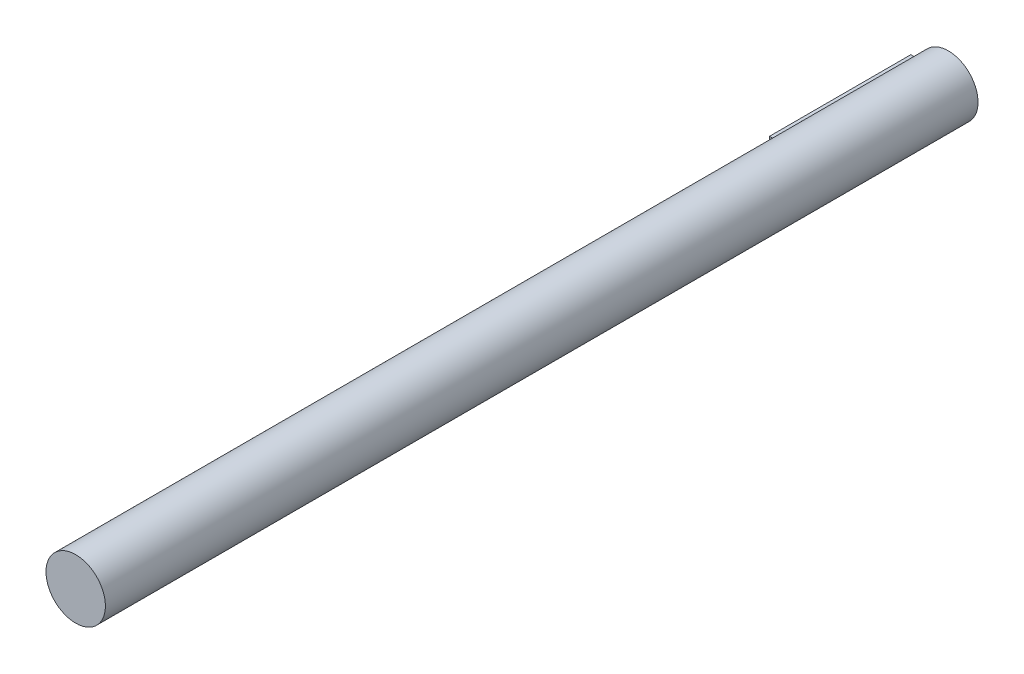
SolidWorks part; units mm, degrees
ref_plane "Front Plane" through (0, 0, 0) normal (0, 0, 1) x (1, 0, 0)
ref_plane "Top Plane" through (0, 0, 0) normal (0, 1, 0) x (1, 0, 0)
ref_plane "Right Plane" through (0, 0, 0) normal (1, 0, 0) x (0, 0, -1)
sketch "Sketch1" plane through (0, 0, 0) normal (0, 0, 1) x (1, 0, 0)
  line L0 (0, 0) -> (0, 3.175)
  line L1 (0, 3.175) -> (-15.621, 3.175)
  line L2 (-15.621, 3.175) -> (-15.621, -2.921)
  line L3 (-15.621, -2.921) -> (0, -2.921)
  line L4 (0, -2.921) -> (0, 0)
  circle A0 centre (0, 0) radius 12.3825
  dimension "D1" = 24.765
  dimension "D2" = 6.096
  dimension "D3" = 3.175
  dimension "D4" = 15.621
extrude "Boss-Extrude4" add sketch "Sketch1" along normal blind 58.928 contours L3 A0 L1 L0 L4 | L1 A0 L3 L4 L0 | A0 L1 L2 L3 region at (-6.1283, 0.1244, 0) region at (1.125, -0.0228, 0) region at (-13.9364, 0.1366, 0)
sketch "Sketch8" plane through (0, 0, 58.928) normal (0, 0, 1) x (1, 0, 0)
  circle A0 centre (0, 0) radius 12.3825
extrude "Boss-Extrude5" add sketch "Sketch8" along normal blind 304.8
